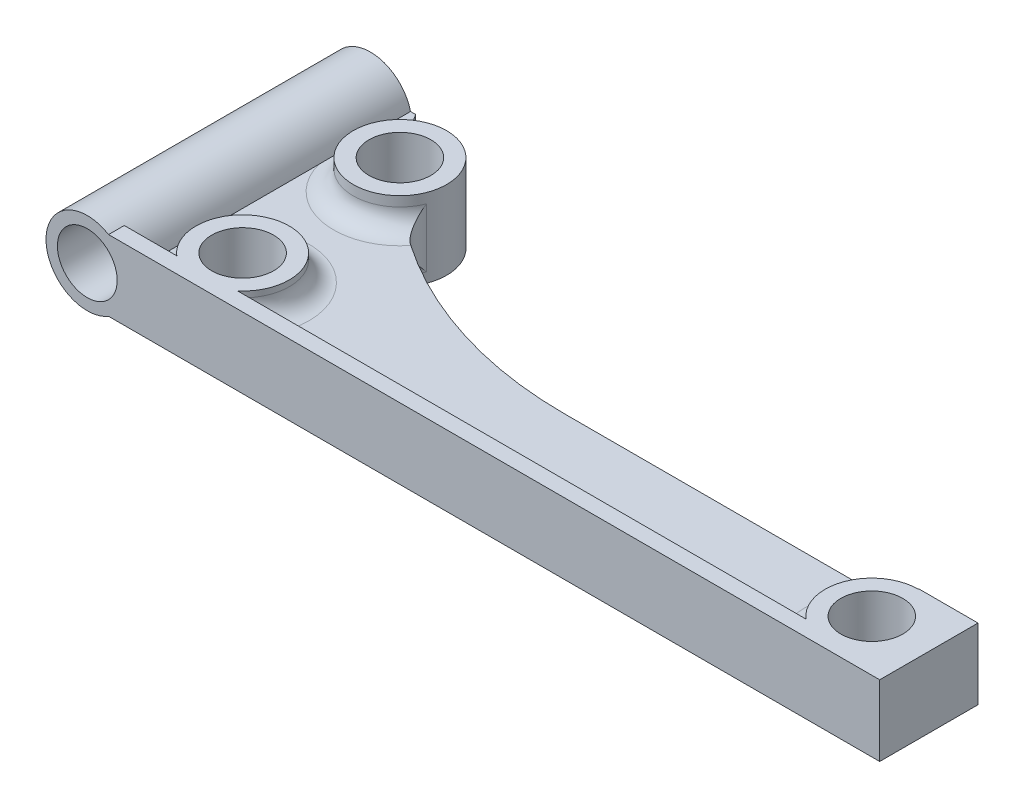
SolidWorks part; units mm, degrees
ref_plane "Front" through (0, 0, 0) normal (0, 0, 1) x (1, 0, 0)
ref_plane "Top" through (0, 0, 0) normal (0, 1, 0) x (1, 0, 0)
ref_plane "Right" through (0, 0, 0) normal (1, 0, 0) x (0, 0, -1)
sketch "Sketch1" plane through (0, 0, 0) normal (0, 0, 1) x (1, 0, 0)
  circle A0 centre (0, 0) radius 10.5
  dimension "D1" = 21
extrude "Boss-Extrude1" add sketch "Sketch1" against normal blind 72
sketch "Sketch2" plane through (0, 0, 0) normal (0, 0, 1) x (1, 0, 0)
  circle A0 centre (0, 0) radius 7.6
  dimension "D1" = 15.2
extrude "Cut-Extrude5" cut sketch "Sketch2" against normal through all
sketch "Sketch3" plane through (0, 0, 0) normal (0, 0, 1) x (1, 0, 0)
  line L1 (5.4083, 9) -> (201.5, 9)
  line L3 (5.4083, -9) -> (201.5, -9)
  line L4 (201.5, 9) -> (201.5, -9)
  circle A0 centre (0, 0) radius 10.5 construction
  arc A1 (5.4083, -9) -> (5.4083, 9) centre (0, 0) ccw
  point P7 (201.5, 0)
  dimension "D2" = 201.5
  dimension "D1" = 18
extrude "Boss-Extrude2" add sketch "Sketch3" against normal blind 72
sketch "Sketch4" plane through (0, 0, -72) normal (0, 0, -1) x (-1, 0, 0)
  line L0 (-201.5, -9) -> (-201.5, 9) construction
  line L1 (-201.5, 2.5) -> (-10.198, 2.5)
  line L2 (-201.5, 2.5) -> (-201.5, -2.5) construction
  line L3 (-201.5, -2.5) -> (-10.198, -2.5) construction
  line L4 (-201.5, 9) -> (5.4083, 9)
  line L5 (-201.5, 9) -> (-5.4083, 9) construction
  line L6 (-201.5, 2.5) -> (-201.5, 9)
  arc A0 (-5.4083, -9) -> (-5.4083, 9) centre (0, 0) ccw construction
  arc A1 (-4.6579, 9.4103) -> (-10.198, -2.5) centre (0, 0) ccw construction
  arc A2 (-10.198, 2.5) -> (5.4083, 9) centre (0, 0) cw
  point P6 (-201.5, 0)
  line M6 (-5.4083, 9) -> (-201.5, 9)
  line M7 (-201.5, 9) -> (-201.5, -9)
  dimension "D1" = 5
extrude "Cut-Extrude2" cut sketch "Sketch4" against normal blind 68 contours L1 A2 M6 M7 region at (104.9837, 5.7628, -72)
mirror "Mirror1" about plane through (0, 0, 0) normal (0, 1, 0) of "Cut-Extrude2"
sketch "Sketch5" plane through (0, 2.5, 0) normal (0, 1, 0) x (1, 0, 0)
  line L0 (201.5, 72) -> (10.198, 72) construction
  line L1 (96.2998, 25) -> (201.5, 25)
  line L2 (201.5, 4) -> (201.5, 72) construction
  line L3 (201.5, 72) -> (11.5, 72)
  line L4 (201.5, 0) -> (5.4083, 0) construction
  line L5 (201.5, 72) -> (201.5, 25)
  arc A0 (11.5, 72) -> (96.2998, 25) centre (96.2998, 125) ccw
  dimension "D2" = 100
  dimension "D1" = 25
  dimension "D3" = 190
extrude "Cut-Extrude3" cut sketch "Sketch5" against normal through all
sketch "Sketch6" plane through (0, -2.5, 0) normal (0, -1, 0) x (1, 0, 0)
  line L0 (201.5, -4) -> (201.5, -25) construction
  line L1 (5.4083, 0) -> (201.5, 0) construction
  circle A0 centre (186.5, -13) radius 7.875
  circle A1 centre (26.5, -13) radius 7.875
  dimension "D1" = 15.75
  dimension "D3" = 160
  dimension "D2" = 15
  dimension "D4" = 13
extrude "Cut-Extrude4" cut sketch "Sketch6" against normal through all
sketch "Sketch7" plane through (0, -2.5, 0) normal (0, -1, 0) x (1, 0, 0)
  circle A0 centre (26.5, -13) radius 7.875 construction
  circle A1 centre (186.5, -13) radius 7.875 construction
  circle A2 centre (26.5, -13) radius 7.875
  circle A3 centre (186.5, -13) radius 7.875
extrude "Extrude-Thin1" add sketch "Sketch7" along normal blind 6.5 thin thin type one direction wall 4
sketch "Sketch8" plane through (0, -2.5, 0) normal (0, -1, 0) x (1, 0, 0)
  line L1 (201.5, -4) -> (201.5, -25) construction
  line L3 (201.5, -4) -> (194.247, -4)
  line L4 (201.5, -4) -> (201.5, -25)
  line L5 (201.5, -25) -> (186.5, -25)
  line L6 (186.5, -25) -> (186.5, -24.875)
  line L7 (201.5, -25) -> (96.2998, -25) construction
  arc A1 (178.753, -4) -> (194.247, -4) centre (186.5, -13) ccw construction
  arc A2 (186.5, -24.875) -> (194.247, -4) centre (186.5, -13) ccw
  arc A3 (178.753, -4) -> (194.247, -4) centre (186.5, -13) ccw construction
extrude "Boss-Extrude3" add sketch "Sketch8" along normal blind 6.5
mirror "Mirror2" about plane through (0, 0, 0) normal (0, 1, 0) of "Boss-Extrude3", "Extrude-Thin1"
sketch "Sketch9" plane through (0, 0, 0) normal (0, -1, 0) x (1, 0, 0)
  circle A0 centre (26.5, -53) radius 11.875
  point P2 (26.5, -13)
  dimension "D1" = 23.75
  dimension "D2" = 40
extrude "Boss-Extrude4" add sketch "Sketch9" along normal blind 10
mirror "Mirror3" about plane through (0, 0, 0) normal (0, 1, 0) of "Boss-Extrude4"
fillet "Fillet1" radius 5 10 edges at (18.2344, 2.5, -44.4738) (26.5, 2.5, -24.875) (106.5, 2.5, -4) (175.3669, 2.5, -17.1316) (106.5, -2.5, -4) (175.3669, -2.5, -17.1316) (26.5, -2.5, -24.875) (18.2344, -2.5, -44.4738) (35.6807, 0, -45.4681) (18.6868, 0, -61.9426)
sketch "Sketch10" plane through (0, 10, 0) normal (0, 1, 0) x (1, 0, 0)
  circle A0 centre (26.5, 53) radius 7.875
  dimension "D1" = 15.75
extrude "Cut-Extrude6" cut sketch "Sketch10" against normal through all
